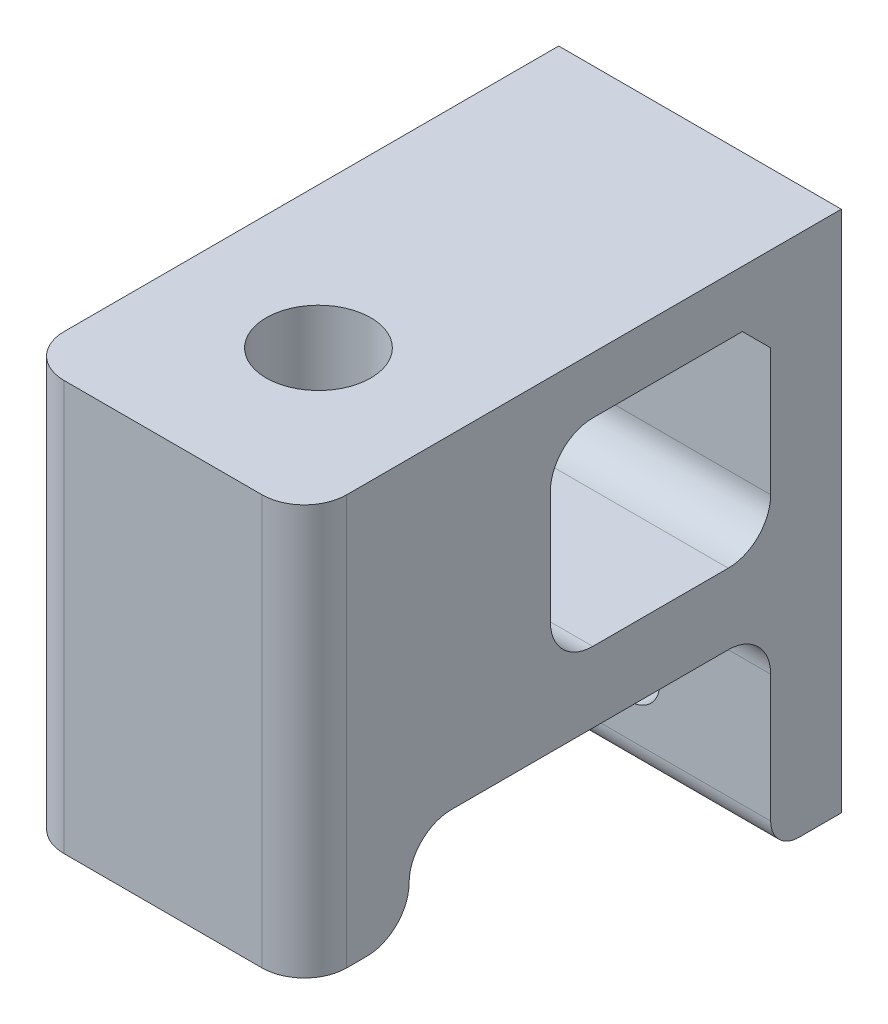
SolidWorks part; units mm, degrees
material "Balsa"
ref_plane "前视基准面" through (0, 0, 0) normal (0, 0, 1) x (1, 0, 0)
ref_plane "上视基准面" through (0, 0, 0) normal (0, 1, 0) x (1, 0, 0)
ref_plane "右视基准面" through (0, 0, 0) normal (1, 0, 0) x (0, 0, -1)
other "Configuration Table"
sketch "Sketch1" plane through (0, 0, 0) normal (0, 0, 1) x (1, 0, 0)
  line L0 (0, -16.5) -> (20, -16.5) construction
  line L1 (0, 0) -> (20, 0)
  line L2 (0, 0) -> (0, -33)
  line L3 (0, -33) -> (20, -33)
  line L4 (20, 0) -> (20, -33)
  circle A0 centre (10, -6.5) radius 2.15
  circle A1 centre (10, -26.5) radius 2.15
  dimension "D3" = 4.3
  dimension "D5" = 20
  dimension "D1" = 20
  dimension "D2" = 33
  dimension "D4" = 10
extrude "Boss-Extrude1" add sketch "Sketch1" along normal blind 5
sketch "Sketch2" plane through (0, 0, 0) normal (0, 0, -1) x (-1, 0, 0)
  line L1 (-20, 0) -> (0, 0)
  line L2 (-20, 0) -> (-20, 4)
  line L3 (-20, 4) -> (0, 4)
  line L4 (0, 0) -> (0, 4)
  dimension "D1" = 4
extrude "Boss-Extrude2" add sketch "Sketch2" against normal blind 38
sketch "Sketch3" plane through (0, 4, 0) normal (0, 1, 0) x (1, 0, 0)
  line L0 (0, 0) -> (20, 0) construction
  circle A0 centre (10, -27) radius 3.7
  point P4 (10, 0)
  dimension "D1" = 27
  dimension "D2" = 7.4
sketch "Sketch4" plane through (0, 0, 0) normal (0, -1, 0) x (1, 0, 0)
  line L0 (20, 38) -> (20, 5) construction
  line L1 (0, 38) -> (20, 38)
  line L2 (0, 38) -> (0, 30.5882)
  line L3 (0, 30.5882) -> (20, 30.5882)
  line L4 (20, 38) -> (20, 30.5882)
extrude "Boss-Extrude3" add sketch "Sketch4" along normal blind 25
fillet "Fillet1" radius 3 2 edges at (0, -10.5, 38) (20, -10.5, 38)
fillet "Fillet2" radius 2 1 edges at (10, -33, 5)
sketch "Sketch5" plane through (20, 0, 0) normal (1, 0, 0) x (0, 0, -1)
  line L0 (-30.5882, 0) -> (-30.5882, -20)
  line L1 (-30.5882, -25) -> (-30.5882, 0) construction
  line L2 (-30.5882, -20) -> (-10.5882, 0)
  line L3 (-30.5882, 0) -> (-5, 0) construction
  line L4 (-10.5882, 0) -> (-30.5882, 0)
  dimension "D1" = 20
  dimension "D2" = 20
fillet "Fillet4" radius 3 1 edges at (10, -25, 30.5882)
chamfer "Chamfer2" distance 2 angle 45 1 edges at (10, 0, 5)
sketch "Sketch8" plane through (0, 0, 5) normal (0, 0, 1) x (1, 0, 0)
  line L0 (0, -2) -> (0, -31) construction
  line L1 (0, -14) -> (20, -14)
  line L2 (0, -14) -> (0, -19)
  line L3 (0, -19) -> (20, -19)
  line L4 (20, -14) -> (20, -19)
  line L5 (20, -31) -> (20, -2) construction
  circle A2 centre (10, -6.5) radius 2.15 construction
  dimension "D1" = 12.5
  dimension "D2" = 5
extrude "Boss-Extrude5" add sketch "Sketch8" along normal up to surface (25.5882 mm away) contours L2 L1 L4 L3 up to face at (10, -11, 30.5882)
fillet "Fillet7" radius 3 3 edges at (10, -19, 5) (10, -19, 30.5882) (10, -14, 5)
ref_plane "Plane1" through (20, -14, 30.5882) normal (1, 0, 0) x (0, 0, -1)
sketch "Sketch12" plane through (0, -14, 0) normal (0, 1, 0) x (1, 0, 0)
  line L0 (0, -35) -> (0, 0) construction
  line L1 (20, -30.5882) -> (0, -30.5882)
  line L2 (20, -30.5882) -> (20, -20.5882)
  line L3 (20, -20.5882) -> (0, -20.5882)
  line L4 (0, -30.5882) -> (0, -20.5882)
  dimension "D1" = 10
extrude "Boss-Extrude6" add sketch "Sketch12" along normal up to surface (14 mm away) up to face at (10, 0, 18.7941)
extrude "Cut-Extrude2" cut sketch "Sketch3" against normal blind 15 contours A0
fillet "Fillet8" radius 3 2 edges at (10, 0, 20.5882) (10, -14, 20.5882)
